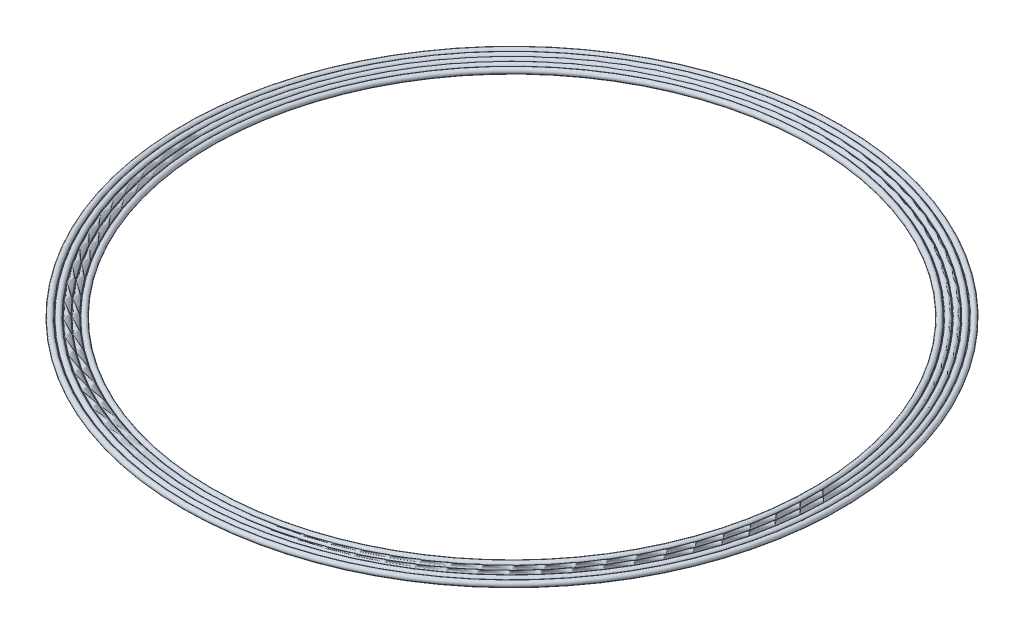
SolidWorks part; units mm, degrees
material "Copper"
ref_plane "Front Plane" through (0, 0, 0) normal (0, 0, 1) x (1, 0, 0)
ref_plane "Top Plane" through (0, 0, 0) normal (0, 1, 0) x (1, 0, 0)
ref_plane "Right Plane" through (0, 0, 0) normal (1, 0, 0) x (0, 0, -1)
sketch "Sketch2" plane through (0, 0, 0) normal (0, 0, 1) x (1, 0, 0)
  line L0 (0, 6.4506) -> (0, -5.0269) construction
  line L1 (0, 0) -> (100, 0) construction
  line L2 (92.5761, 0.2) -> (92.7739, 0.2)
  line L3 (92.5761, -0.2) -> (92.7739, -0.2)
  line L4 (94.4261, -0.2) -> (94.6239, -0.2)
  line L5 (94.4261, 0.2) -> (94.6239, 0.2)
  line L6 (96.2761, 0.2) -> (96.4739, 0.2)
  line L7 (96.2761, -0.2) -> (96.4739, -0.2)
  line L8 (98.1261, -0.2) -> (98.3239, -0.2)
  line L9 (98.1261, 0.2) -> (98.3239, 0.2)
  arc A0 (98.3239, -0.2) -> (98.3239, 0.2) centre (99.15, 0) ccw
  arc A1 (96.4739, -0.2) -> (98.1261, -0.2) centre (97.3, 0) ccw
  arc A2 (94.6239, -0.2) -> (96.2761, -0.2) centre (95.45, 0) ccw
  arc A3 (92.7739, -0.2) -> (94.4261, -0.2) centre (93.6, 0) ccw
  arc A4 (92.5761, 0.2) -> (92.5761, -0.2) centre (91.75, 0) ccw
  arc A5 (94.4261, 0.2) -> (92.7739, 0.2) centre (93.6, 0) ccw
  arc A6 (96.2761, 0.2) -> (94.6239, 0.2) centre (95.45, 0) ccw
  arc A7 (98.1261, 0.2) -> (96.4739, 0.2) centre (97.3, 0) ccw
  point P6 (92.675, -0.2)
  point P15 (90.9, 0)
  dimension "D1" = 1.7
  dimension "D2" = 100
  dimension "D3" = 9.1
  dimension "D4" = 1.85
  dimension "D5" = 1.85
  dimension "D6" = 1.85
  dimension "D7" = 0.2
  dimension "D8" = 0.2
revolve "Revolve1" add sketch "Sketch2" angle 360 about L0
ref_axis "Axis1" through (0, 6.4506, 0) along (0, -1, 0)
equation "\"D4@Sketch2\"=(\"D3@Sketch2\" -\"D1@Sketch2\")/4"
equation "\"D5@Sketch2\"=\"D4@Sketch2\""
equation "\"D6@Sketch2\"=\"D4@Sketch2\""
